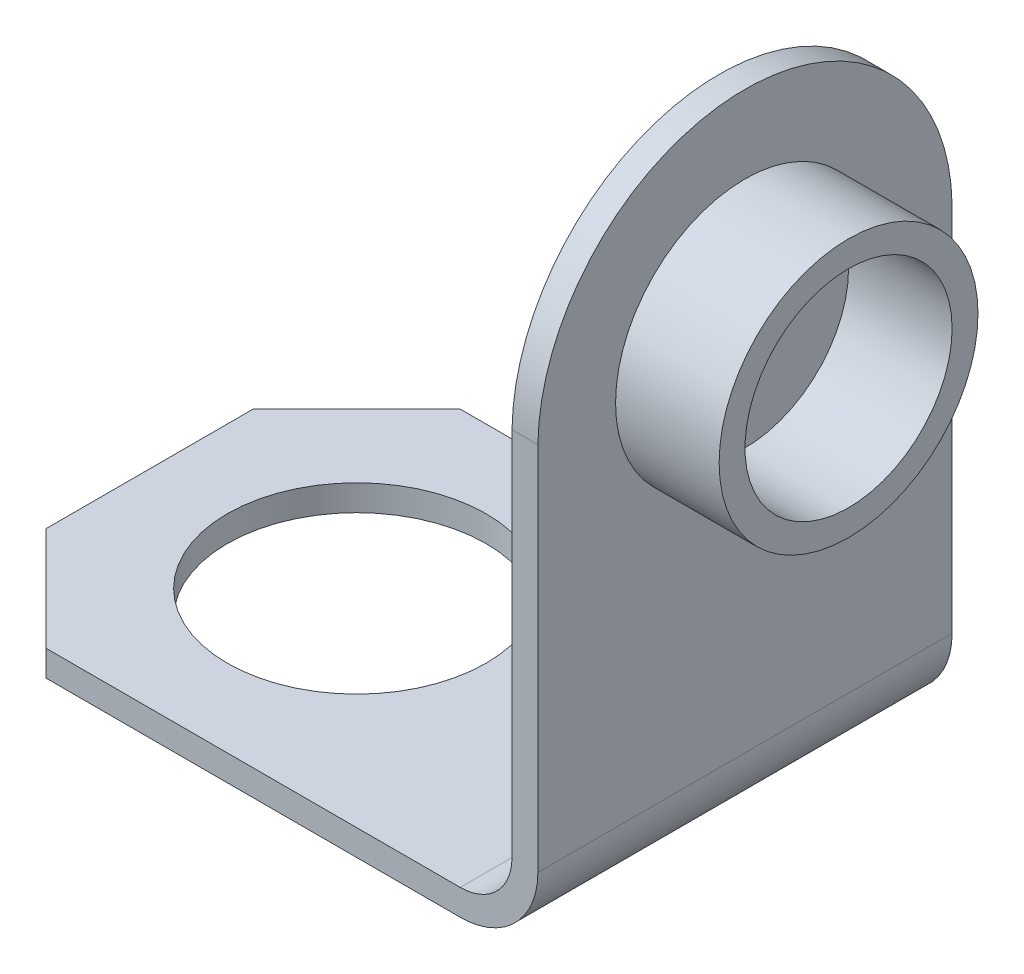
SolidWorks part; units mm, degrees
ref_plane "Front Plane" through (0, 0, 0) normal (0, 0, 1) x (1, 0, 0)
ref_plane "Top Plane" through (0, 0, 0) normal (0, 1, 0) x (1, 0, 0)
ref_plane "Right Plane" through (0, 0, 0) normal (1, 0, 0) x (0, 0, -1)
sketch "Sketch1" plane through (0, 0, 0) normal (0, 0, 1) x (1, 0, 0)
  line L0 (0, 0) -> (50, 0)
  line L1 (57.5, 7.5) -> (57.5, 63)
  line L2 (0, 2.5) -> (50, 2.5)
  line L3 (55, 7.5) -> (55, 63)
  line L4 (55, 63) -> (57.5, 63)
  line L5 (0, 2.5) -> (0, 0)
  arc A0 (50, 0) -> (57.5, 7.5) centre (50, 7.5) ccw
  arc A1 (50, 2.5) -> (55, 7.5) centre (50, 7.5) ccw
  dimension "D1" = 50
  dimension "D4" = 7.5
  dimension "D3" = 63
  dimension "D2" = 2.5
extrude "Boss-Extrude1" add sketch "Sketch1" against normal blind 40
sketch "Sketch2" plane through (57.5, 0, 0) normal (1, 0, 0) x (0, 0, -1)
  line L2 (0, 63) -> (0, 0.772) construction
  line L3 (20, 63) -> (20, 7.5) construction
  line L7 (0, 63) -> (0, 7.5)
  line L8 (40, 63) -> (0, 63)
  line L9 (40, 7.5) -> (40, 63)
  line L10 (0, 7.5) -> (40, 7.5)
  line L11 (0, 63) -> (0, 7.5)
  line L12 (40, 63) -> (0, 63)
  line L13 (40, 7.5) -> (40, 63)
  line L14 (0, 7.5) -> (40, 7.5)
  arc A0 (0, 42.715) -> (40, 42.715) centre (20, 42.998) cw
  circle A1 centre (20, 42.998) radius 10
  circle A2 centre (20, 42.998) radius 12.5
  point P3 (0, 0)
  point P4 (20, 43.501)
  point P5 (20, 63)
  point P17 (0, 0)
  point P18 (20.7249, 42.998)
  line M19 (0, 63) -> (0, 7.5)
  line M21 (40, 7.5) -> (40, 63)
  line M22 (40, 63) -> (0, 63)
  dimension "D1" = 20.002
  dimension "D3" = 20
  dimension "D4" = 25
  dimension "D2" = 0
extrude "Cut-Extrude2" cut sketch "Sketch2" against normal through all contours A0 L12 M19 | A0 M22 M21 region at (57.5, 58.5347, -4.4679) region at (57.5, 58.5347, -35.5321)
extrude "Boss-Extrude2" add sketch "Sketch2<4>" along normal blind 10 contours L2 A2 A1 | A2 L2 A1 region at (57.5, 42.998, -7.8536)
sketch "Sketch2<4>" plane through (57.5, 0, 0) normal (1, 0, 0) x (0, 0, -1) same geometry as "Sketch2"
chamfer "Chamfer1" distance 10 angle 45 2 edges at (0, 1.25, -40) (0, 1.25, 0)
sketch "Sketch3" plane through (0, 2.5, 0) normal (0, 1, 0) x (1, 0, 0)
  line L0 (0, 20) -> (50, 20) construction
  line L6 (0, 30) -> (0, 10)
  line L7 (10, 40) -> (0, 30)
  line L8 (50, 40) -> (10, 40)
  line L9 (50, 0) -> (50, 40)
  line L10 (10, 0) -> (50, 0)
  line L11 (0, 10) -> (10, 0)
  line L12 (0, 30) -> (0, 10)
  line L13 (10, 40) -> (0, 30)
  line L14 (50, 40) -> (10, 40)
  line L15 (50, 0) -> (50, 40)
  line L16 (10, 0) -> (50, 0)
  line L17 (0, 10) -> (10, 0)
  circle A0 centre (20, 20) radius 12.5
  dimension "D2" = 25
  dimension "D3" = 20
  dimension "D1" = 0
extrude "Cut-Extrude3" cut sketch "Sketch3" against normal through all both and the other way through all contours A0
